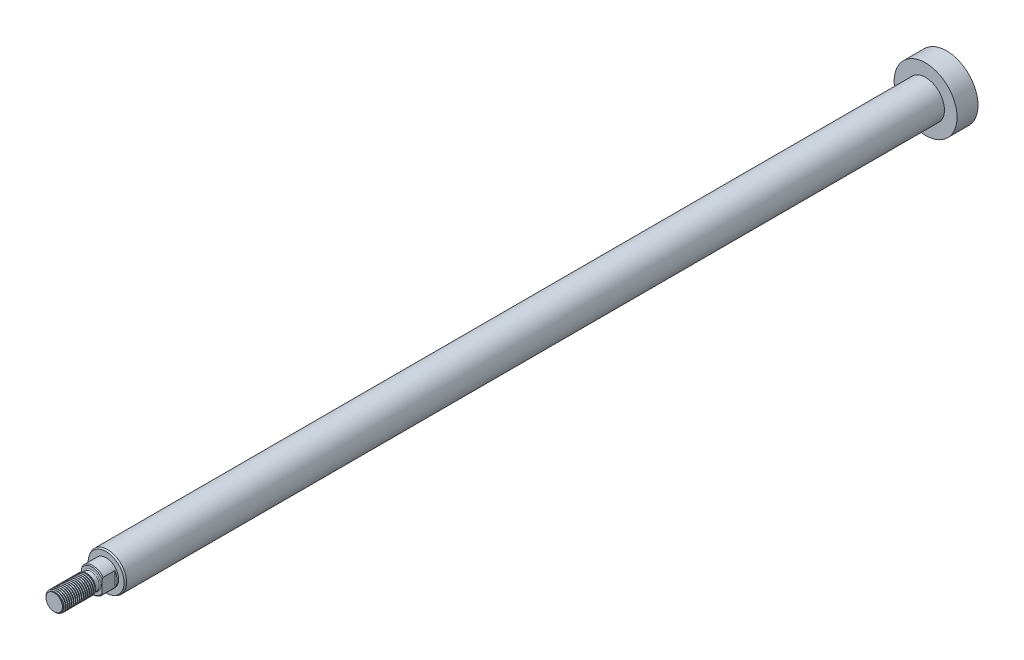
SolidWorks part; units mm, degrees
ref_plane "Front Plane" through (0, 0, 0) normal (0, 0, 1) x (1, 0, 0)
ref_plane "Top Plane" through (0, 0, 0) normal (0, 1, 0) x (1, 0, 0)
ref_plane "Right Plane" through (0, 0, 0) normal (1, 0, 0) x (0, 0, -1)
sketch "Sketch1" plane through (0, 0, 0) normal (1, 0, 0) x (0, 0, -1)
  line L0 (-29.5, 0) -> (-29.5, 7.5)
  line L1 (-29.5, 7.5) -> (-29, 8)
  line L2 (-29, 8) -> (-20.5, 8)
  line L3 (-20.5, 8) -> (-20.5, 11.4226)
  line L4 (-20.5, 11.4226) -> (-19.5, 12)
  line L5 (-19.5, 12) -> (500.6667, 12)
  line L6 (500.6667, 12) -> (500.6667, 20)
  line L7 (500.6667, 20) -> (514, 20)
  line L8 (514, 20) -> (514, 0)
  line L9 (514, 0) -> (-29.5, 0)
  line L10 (514, 0) -> (-29.5, 0) construction
revolve "Revolve1" add sketch "Sketch1" angle 360 about L10 reverse direction yes
sketch "Sketch2" plane through (0, 0, 0) normal (0, 1, 0) x (1, 0, 0)
  line L0 (-9.5, -21.5) -> (-9.5, -32.5)
  line L1 (-9.5, -32.5) -> (9.5, -32.5)
  line L2 (9.5, -32.5) -> (9.5, -21.5)
  line L3 (9.5, -21.5) -> (6.5, -21.5)
  line L4 (6.5, -21.5) -> (6.5, -29.5)
  line L5 (6.5, -29.5) -> (-6.5, -29.5)
  line L6 (-6.5, -29.5) -> (-6.5, -21.5)
  line L7 (-6.5, -21.5) -> (-9.5, -21.5)
extrude "Cut-Extrude1" cut sketch "Sketch2" along normal blind 16 and the other way blind 16
sketch "Sketch3" plane through (0, 0, 0) normal (1, 0, 0) x (0, 0, -1)
  line L0 (-53.5, 0) -> (-53.5, 5.233)
  line L1 (-53.5, 5.233) -> (-52.733, 6)
  line L2 (-52.733, 6) -> (-33.267, 6)
  line L3 (-33.267, 6) -> (-32.5, 5.233)
  line L4 (-32.5, 5.233) -> (-30.1, 5.233)
  line L5 (-29.5, 5.833) -> (-29.5, 0)
  line L6 (-29.5, 0) -> (-53.5, 0)
  line L7 (-29.5, 0) -> (-53.5, 0) construction
  arc A0 (-30.1, 5.233) -> (-29.5, 5.833) centre (-30.1, 5.833) ccw
revolve "Revolve2" add sketch "Sketch3" angle 360 about L7 reverse direction yes
cosmetic thread "Cosmetic Thread1" parameters "D1"=21, "D2"=10.466
ref_plane "Plane1" through (0, 0, -514) normal (0, 0, 1) x (1, 0, 0)
ref_plane "Plane2" through (0, 0, 37.5) normal (0, 0, 1) x (1, 0, 0)
ref_plane "ANBAU XY" through (0, 0, -514) normal (0, 0, -1) x (-1, 0, 0)
ref_plane "ANBAU XZ" through (0, 0, 0) normal (0, 1, 0) x (1, 0, 0)
ref_plane "ANBAU YZ" through (0, 0, 0) normal (1, 0, 0) x (0, 0, -1)
ref_axis "ANBAU X" through (-80.9, 0, -514) along (1, 0, 0)
ref_axis "ANBAU Y" through (0, 50, -514) along (0, -1, 0)
ref_axis "ANBAU Z" through (0, 0, -80.9) along (0, 0, 1)
sketch3d "ANBAU"
  point P0 (0, 0, -514)
ref_plane "NUT XY" through (0, 0, 37.5) normal (0, 0, -1) x (-1, 0, 0)
ref_plane "NUT XZ" through (0, 0, 0) normal (0, 1, 0) x (1, 0, 0)
ref_plane "NUT YZ" through (0, 0, 0) normal (1, 0, 0) x (0, 0, -1)
ref_axis "NUT X" through (-80.9, 0, 37.5) along (1, 0, 0)
ref_axis "NUT Y" through (0, 50, 37.5) along (0, -1, 0)
ref_axis "NUT Z" through (0, 0, -80.9) along (0, 0, 1)
sketch3d "NUT"
  point P0 (0, 0, 37.5)
other "Freeze***"
thread "Thread1" pitch 1.25 method cut profile "Thread Profile1" start angle 0, offset 5, length 25, pitch 1.25, diameter 12
ref_plane "Plane3" through (-6, 0, 57.733) normal (0, -1, 0) x (-1, 0, 0)
sketch "Thread Profile1" plane through (-6, 0, 57.733) normal (0, -1, 0) x (-1, 0, 0)
  line L0 (0, 0) -> (0, 1.25) construction
  line L11 (0, 0) -> (0, 1.0937)
  line L12 (0, 1.0937) -> (-0.6766, 0.7031)
  line L13 (-0.6766, 0.7031) -> (-0.6766, 0.3906)
  line L15 (-0.6766, 0.3906) -> (0, 0)
  line L17 (-0.6766, 0.5469) -> (0, 0.5469) construction
  point P2 (0, 0)
  dimension "Pitch" = 1.25
  dimension "Profile_Angle" = 60
  dimension "Profile_Land" = 0.3125
  dimension "Profile_Height" = 0.6766
